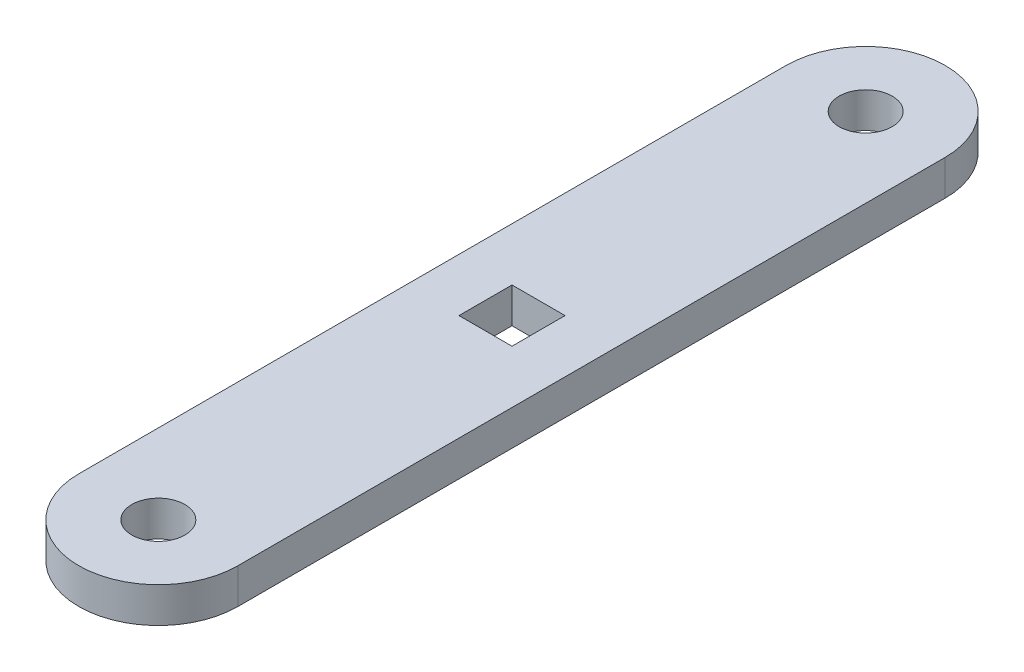
SolidWorks part; units mm, degrees
ref_plane "Front Plane" through (0, 0, 0) normal (0, 0, 1) x (1, 0, 0)
ref_plane "Top Plane" through (0, 0, 0) normal (0, 1, 0) x (1, 0, 0)
ref_plane "Right Plane" through (0, 0, 0) normal (1, 0, 0) x (0, 0, -1)
sketch "Sketch1" plane through (0, 0, 0) normal (0, 1, 0) x (1, 0, 0)
  line L1 (-225, -1000) -> (225, -1000)
  line L2 (-225, -1000) -> (-225, 1000)
  line L3 (-225, 1000) -> (225, 1000)
  line L4 (225, -1000) -> (225, 1000)
  line L5 (-225, -1000) -> (225, 1000) construction
  line L6 (-225, 1000) -> (225, -1000) construction
  arc A0 (225, -1000) -> (-225, -1000) centre (0, -1000) cw
  arc A1 (225, 1000) -> (-225, 1000) centre (0, 1000) ccw
  point P0 (0, 0)
  dimension "D1" = 2000
  dimension "D2" = 450
extrude "Boss-Extrude1" add sketch "Sketch1" along normal blind 100 contours L1 L4 L3 L2 | L3 A1 | A0 L1 region at (0, 0, 0) region at (0, 0, 1095.493) region at (0, 0, -1095.493)
sketch "Sketch2" plane through (0, 100, 0) normal (0, 1, 0) x (1, 0, 0)
  line L0 (-225, -1000) -> (225, -1000)
  line L1 (-225, -1000) -> (-225, 1000) construction
  circle A0 centre (0, -1000) radius 75
sketch "Sketch3" plane through (0, 100, 0) normal (0, 1, 0) x (1, 0, 0)
  line L0 (-225, 1000) -> (225, 1000)
  circle A0 centre (0, 1000) radius 75
extrude "Cut-Extrude2" cut sketch "Sketch3" against normal blind 250 contours L0 A0 | L0 A0 region at (0, 100, -1031.831) region at (0, 100, -968.169)
extrude "Cut-Extrude4" cut sketch "Sketch2" against normal through all contours L0 A0 | L0 A0 region at (0, 100, 968.169) region at (0, 100, 1031.831)
sketch "Sketch4" plane through (0, 100, 0) normal (0, 1, 0) x (1, 0, 0)
  line L1 (-75, -75) -> (75, -75)
  line L2 (-75, -75) -> (-75, 75)
  line L3 (-75, 75) -> (75, 75)
  line L4 (75, -75) -> (75, 75)
  line L5 (-75, -75) -> (75, 75) construction
  line L6 (-75, 75) -> (75, -75) construction
  point P0 (0, 0)
  dimension "D1" = 150
  dimension "D2" = 150
extrude "Cut-Extrude5" cut sketch "Sketch4" against normal through all
